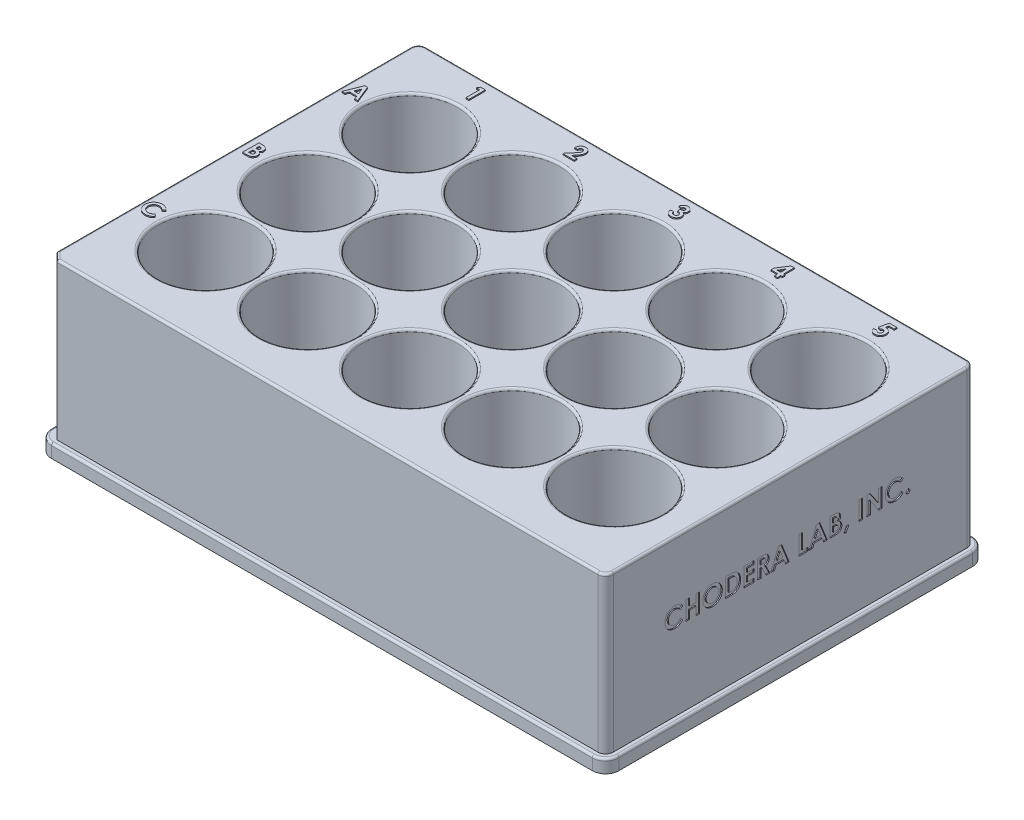
SolidWorks part; units mm, degrees
ref_plane "Front Plane" through (0, 0, 0) normal (0, 0, 1) x (1, 0, 0)
ref_plane "Top Plane" through (0, 0, 0) normal (0, 1, 0) x (1, 0, 0)
ref_plane "Right Plane" through (0, 0, 0) normal (1, 0, 0) x (0, 0, -1)
sketch "Sketch1" plane through (0, 0, 0) normal (0, 1, 0) x (1, 0, 0)
  line L0 (-63.875, -42.8) -> (63.875, 42.8) construction
  line L1 (-63.875, -42.8) -> (63.875, -42.8)
  line L2 (-63.875, -42.8) -> (-63.875, 42.8)
  line L3 (-63.875, 42.8) -> (63.875, 42.8)
  line L4 (63.875, -42.8) -> (63.875, 42.8)
  point P4 (0, 0)
  dimension "D1" = 85.6
  dimension "D2" = 127.75
extrude "Boss-Extrude1" add sketch "Sketch1" along normal blind 38.1
fillet "Fillet1" radius 3 4 edges at (-63.875, 19.05, -42.8) (-63.875, 19.05, 42.8) (63.875, 19.05, 42.8) (63.875, 19.05, -42.8)
sketch "Sketch3" plane through (0, 38.1, 0) normal (0, 1, 0) x (1, 0, 0)
  line L0 (-63.875, 39.8) -> (-63.875, -39.8) construction
  line L1 (60.875, 42.8) -> (-60.875, 42.8) construction
  line L2 (63.875, -39.8) -> (63.875, 39.8) construction
  line L3 (-60.875, -42.8) -> (60.875, -42.8) construction
  line L4 (-63.875, 39.8) -> (-63.875, -39.8)
  line L5 (60.875, 42.8) -> (-60.875, 42.8)
  line L6 (63.875, -39.8) -> (63.875, 39.8)
  line L7 (-60.875, -42.8) -> (60.875, -42.8)
  line L8 (-62.625, 39.8) -> (-62.625, -39.8)
  line L9 (-60.875, -41.55) -> (60.875, -41.55)
  line L10 (62.625, -39.8) -> (62.625, 39.8)
  line L11 (60.875, 41.55) -> (-60.875, 41.55)
  line L12 (-62.625, -39.8) -> (-60.875, -41.55)
  arc A0 (-60.875, 42.8) -> (-63.875, 39.8) centre (-60.875, 39.8) ccw construction
  arc A1 (63.875, 39.8) -> (60.875, 42.8) centre (60.875, 39.8) ccw construction
  arc A2 (60.875, -42.8) -> (63.875, -39.8) centre (60.875, -39.8) ccw construction
  arc A3 (-63.875, -39.8) -> (-60.875, -42.8) centre (-60.875, -39.8) ccw construction
  arc A4 (-60.875, 42.8) -> (-63.875, 39.8) centre (-60.875, 39.8) ccw
  arc A5 (63.875, 39.8) -> (60.875, 42.8) centre (60.875, 39.8) ccw
  arc A6 (60.875, -42.8) -> (63.875, -39.8) centre (60.875, -39.8) ccw
  arc A7 (-63.875, -39.8) -> (-60.875, -42.8) centre (-60.875, -39.8) ccw
  arc A9 (60.875, -41.55) -> (62.625, -39.8) centre (60.875, -39.8) ccw
  arc A10 (62.625, 39.8) -> (60.875, 41.55) centre (60.875, 39.8) ccw
  arc A11 (-60.875, 41.55) -> (-62.625, 39.8) centre (-60.875, 39.8) ccw
  arc A12 (-62.625, -39.8) -> (-60.875, -41.55) centre (-60.875, -39.8) ccw construction
  dimension "D1" = 1.25
extrude "Cut-Extrude2" cut sketch "Sketch3" against normal blind 35.1
sketch "Sketch5" plane through (0, 38.1, 0) normal (0, 1, 0) x (1, 0, 0)
  circle A0 centre (-46, 23) radius 10.75
  circle A1 centre (-23, 23) radius 10.75
  circle A2 centre (0, 23) radius 10.75
  circle A3 centre (23, 23) radius 10.75
  circle A4 centre (46, 23) radius 10.75
  circle A5 centre (-23, 0) radius 10.75
  circle A6 centre (0, 0) radius 10.75
  circle A7 centre (23, 0) radius 10.75
  circle A8 centre (46, 0) radius 10.75
  circle A9 centre (-23, -23) radius 10.75
  circle A10 centre (0, -23) radius 10.75
  circle A11 centre (23, -23) radius 10.75
  circle A12 centre (46, -23) radius 10.75
  circle A13 centre (-46, 0) radius 10.75
  circle A14 centre (-46, -23) radius 10.75
  dimension "D1" = 21.5
  dimension "D2" = 5
  dimension "D3" = 3
  dimension "D4" = 23
  dimension "D5" = 23
extrude "Cut-Extrude3" cut sketch "Sketch5" against normal up to surface (35.1 mm away) up to face at (0.0453, 3, -0.0453)
fillet "Fillet3" radius 0.5 23 edges at (0, 38.1, -41.55) (62.1124, 38.1, -41.0374) (62.625, 38.1, 0) (62.1124, 38.1, 41.0374) (0, 38.1, 41.55) (-61.75, 38.1, 40.675) (-62.625, 38.1, 0) (-62.1124, 38.1, -41.0374) (-46, 38.1, -12.25) (0, 38.1, 10.75) (-23, 38.1, -12.25) (0, 38.1, -12.25) (23, 38.1, -12.25) (46, 38.1, -12.25) (-23, 38.1, 10.75) (23, 38.1, 10.75) (46, 38.1, 10.75) (-23, 38.1, 33.75) (0, 38.1, 33.75) (23, 38.1, 33.75) (46, 38.1, 33.75) (-46, 38.1, 10.75) (-46, 38.1, 33.75)
fillet "Fillet5" radius 0.5 8 edges at (-62.9963, 3, 41.9213) (-63.875, 3, 0) (-62.9963, 3, -41.9213) (0, 3, -42.8) (62.9963, 3, -41.9213) (63.875, 3, 0) (62.9963, 3, 41.9213) (0, 3, 42.8)
sketch "Sketch6" plane through (0, 38.1, 0) normal (0, 1, 0) x (1, 0, 0)
  line L0 (0, 41.05) -> (0.1036, -41.05) construction
  line L1 (60.875, 41.05) -> (-60.875, 41.05) construction
  line L2 (-60.6679, -41.05) -> (60.875, -41.05) construction
  line L3 (-62.125, 0.1036) -> (62.125, 0) construction
  line L4 (-62.125, 39.8) -> (-62.125, -39.5929) construction
  line L5 (62.125, -39.8) -> (62.125, 39.8) construction
  line L6 (-62.125, 23.1036) -> (62.125, 23.1036) construction
  line L7 (-62.125, -22.8964) -> (62.125, -22.8964) construction
  line L8 (-49.7992, 23.1036) -> (-65.7992, 23.1036) construction
  line L9 (-40.4824, 0.0855) -> (-59.8284, 0.1016) construction
  line L10 (-40.5, -23) -> (-56.5, -22.8964) construction
  line L11 (-49.7992, 23.1036) -> (-49.7992, 35.8536) construction
  line L12 (-49.7992, 35.8536) -> (-34.1408, 35.8536) construction
  line L13 (-34.1408, 35.8536) -> (-11.8592, 35.8536) construction
  line L14 (-23, 35.8536) -> (23.0131, 35.8536) construction
  line L15 (14.68, 35.8536) -> (31.3462, 35.8536) construction
  line L16 (-62.125, 0.1036) -> (-57.25, 0) construction
  line L17 (-62.125, 23.1036) -> (-57.25, 23.1036) construction
  line L18 (-62.125, -22.8964) -> (-57.2495, -22.8964) construction
  line L19 (-56.25, 35.8536) -> (-35.7015, 35.8536) construction
  line L20 (-23, 23) -> (-23, 33.75) construction
  line L21 (-23, 33.75) -> (-23, 41.05) construction
  line L22 (23.0131, 23.1036) -> (23.0131, 41.05) construction
  line L23 (46, 23) -> (46, 41.05) construction
  line L24 (35.6838, 35.8536) -> (56.3162, 35.8536) construction
  circle A0 centre (-46, 0) radius 11.25 construction
  circle A1 centre (-46, -23) radius 11.25 construction
  circle A3 centre (-23, 23) radius 10.75 construction
  text T0 "<b>A</b>" font "Century Gothic" height in points 14
  text T1 "<b>B</b>" font "Century Gothic" height in points 14
  text T2 "<b>C</b>" font "Century Gothic" height in points 14
  text T3 "<b>1</b>" font "Century Gothic" height in points 14
  text T4 "<b>2</b>" font "Century Gothic" height in points 14
  text T5 "<b>3</b>" font "Century Gothic" height in points 14
  text T6 "<b>4</b>" font "Century Gothic" height in points 14
  text T7 "<b>5</b>" font "Century Gothic" height in points 14
  point P46 (0.0066, 35.8536)
  point P54 (23.0131, 35.8536)
  point P60 (46, 35.8536)
  dimension "D1" = 23
  dimension "D2" = 23
  dimension "D3" = 16
  dimension "D4" = 12.75
shell "Shell1" thickness 1 removed face at (0, 0, 0)
ref_plane "Plane1" through (13.5, 0, 0) normal (1, 0, 0) x (0, 0, -1)
ref_plane "Plane2" through (40.5, 0, 0) normal (1, 0, 0) x (0, 0, -1)
ref_plane "Plane3" through (-13.5, 0, 0) normal (1, 0, 0) x (0, 0, -1)
ref_plane "Plane4" through (-40.5, 0, 0) normal (1, 0, 0) x (0, 0, -1)
sketch "Sketch10" plane through (62.625, 0, 0) normal (1, 0, 0) x (0, 0, -1)
  line L0 (-39.8, 20.3) -> (39.8, 20.3) construction
  line L1 (-39.8, 3) -> (-39.8, 37.6) construction
  line L2 (39.8, 3) -> (39.8, 37.6) construction
  text T0 "<b>CHODERA LAB, INC.</b>" font "Century Gothic" height in points 16
extrude "Cut-Extrude4" cut sketch "Sketch10" against normal blind 0.25
extrude "Boss-Extrude2" add sketch "Sketch6" along normal blind 0.25
sketch "Sketch12" plane through (0, 38.1, 0) normal (0, 1, 0) x (1, 0, 0)
  line L0 (-46, 34.25) -> (-46, 41.05)
  line L4 (-23, 34.25) -> (-23, 41.05)
  line L5 (0, 34.25) -> (0, 41.05)
  line L6 (23, 34.25) -> (23, 41.05)
  line L7 (46, 34.25) -> (46, 41.05)
  line L9 (46, -34.25) -> (46, -41.05)
  line L11 (23, -34.25) -> (23, -41.05)
  line L12 (0, -34.25) -> (0, -41.05)
  line L14 (-23, -34.25) -> (-23, -41.05)
  line L15 (-46, -34.25) -> (-46, -41.05)
  line L16 (60.875, 41.05) -> (-60.875, 41.05) construction
  line L17 (-60.6679, -41.05) -> (60.875, -41.05) construction
  line L18 (60.875, 41.05) -> (-60.875, 41.05) construction
  line L19 (-60.6679, -41.05) -> (60.875, -41.05) construction
  circle A26 centre (0, 23) radius 11.25 construction
  circle A27 centre (23, 23) radius 11.25 construction
  circle A28 centre (46, 23) radius 11.25 construction
  circle A29 centre (46, -23) radius 11.25 construction
  circle A30 centre (23, -23) radius 11.25 construction
  circle A31 centre (0, -23) radius 11.25 construction
  circle A32 centre (-23, -23) radius 11.25 construction
  circle A33 centre (-46, -23) radius 11.25 construction
  circle A34 centre (-46, 23) radius 11.25 construction
  circle A36 centre (-23, 23) radius 11.25 construction
extrude "Extrude-Thin2" add sketch "Sketch12" against normal up to surface (36.1 mm away) thin thin type mid plane wall 1
